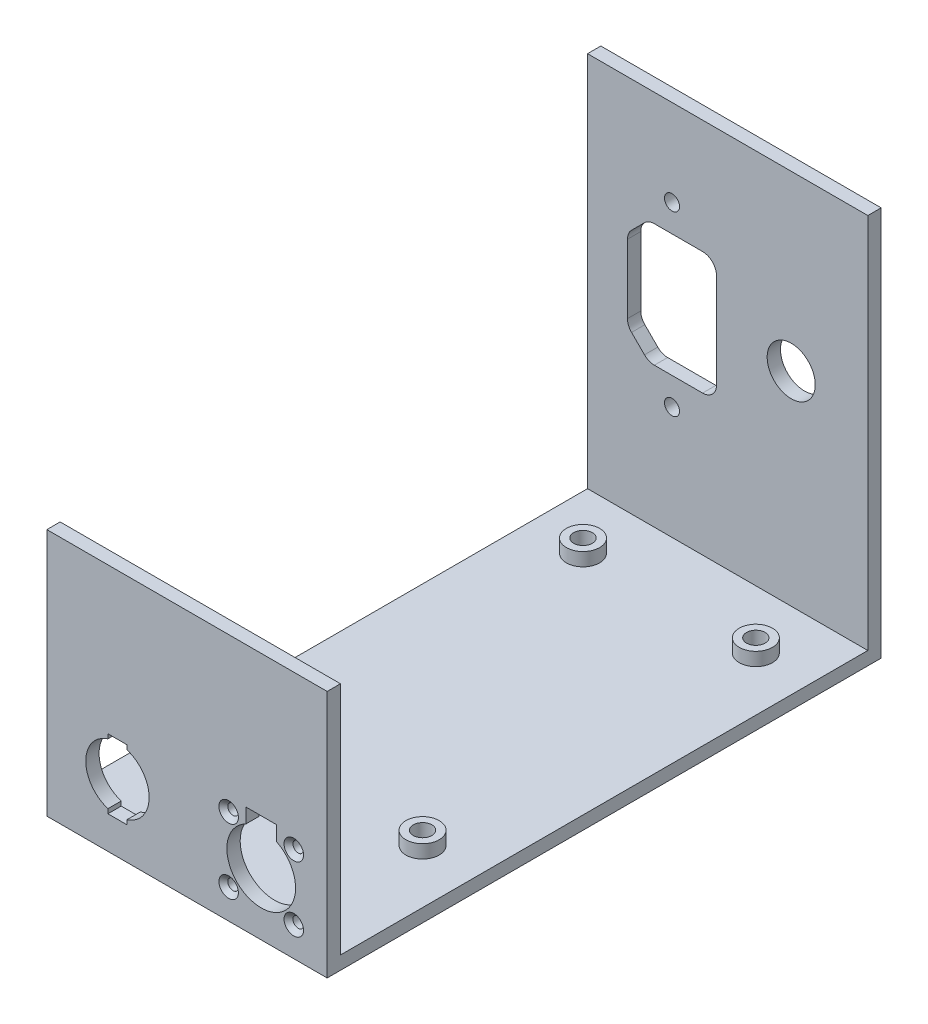
SolidWorks part; units mm, degrees
ref_plane "Спереди" through (0, 0, 0) normal (0, 0, 1) x (1, 0, 0)
ref_plane "Сверху" through (0, 0, 0) normal (0, 1, 0) x (1, 0, 0)
ref_plane "Справа" through (0, 0, 0) normal (1, 0, 0) x (0, 0, -1)
sketch "Эскиз2" plane through (0, 0, 0) normal (0, -1, 0) x (1, 0, 0)
  circle A0 centre (19.5, 37.6) radius 3.75
  circle A1 centre (19.5, -37.6) radius 3.75
  circle A2 centre (-19.5, -37.6) radius 3.75
  circle A3 centre (-19.5, 37.6) radius 3.75
  dimension "D1" = 7.5
extrude "Бобышка-Вытянуть1" add sketch "Эскиз2" along normal blind 3
sketch "Эскиз3" plane through (0, -3, 0) normal (0, -1, 0) x (1, 0, 0)
  line L0 (26.625, 41.25) -> (26.625, -41.25) construction
  line L1 (-31.625, 71.25) -> (31.625, 71.25)
  line L2 (-31.625, 71.25) -> (-31.625, -53.75)
  line L3 (-31.625, -53.75) -> (31.625, -53.75)
  line L4 (31.625, 71.25) -> (31.625, -53.75)
  line L5 (-31.625, 71.25) -> (31.625, -53.75) construction
  line L6 (-31.625, -53.75) -> (31.625, 71.25) construction
  line L8 (-23.625, 41.25) -> (23.625, 41.25) construction
  line L9 (-26.625, 41.25) -> (-26.625, -41.25) construction
  point P0 (0, 8.75)
  dimension "D1" = 5
  dimension "D2" = 125
  dimension "D3" = 30
  dimension "D4" = 5
extrude "Бобышка-Вытянуть2" add sketch "Эскиз3" along normal blind 3
sketch "Эскиз4" plane through (0, 0, 0) normal (0, 1, 0) x (1, 0, 0)
  circle A0 centre (19.5, 37.6) radius 2.1
  circle A1 centre (19.5, -37.6) radius 2.1
  circle A2 centre (-19.5, -37.6) radius 2.1
  circle A3 centre (-19.5, 37.6) radius 2.1
  dimension "D1" = 4.2
extrude "Вырез-Вытянуть1" cut sketch "Эскиз4" against normal blind 4
sketch "Эскиз5" plane through (0, -3, 0) normal (0, 1, 0) x (1, 0, 0)
  line L0 (31.625, 53.75) -> (31.625, -71.25) construction
  line L1 (-31.625, -71.25) -> (31.625, -71.25)
  line L2 (-31.625, -71.25) -> (-31.625, -68.25)
  line L3 (-31.625, -68.25) -> (31.625, -68.25)
  line L4 (31.625, -71.25) -> (31.625, -68.25)
  dimension "D1" = 3
extrude "Бобышка-Вытянуть3" add sketch "Эскиз5" along normal blind 53
sketch "Эскиз8" plane through (0, 0, 71.25) normal (0, 0, 1) x (1, 0, 0)
  line L6 (20.1954, 14.9397) -> (20.1954, 18.25)
  line L7 (20.1954, 18.25) -> (13.2954, 18.25)
  line L8 (13.2954, 18.25) -> (13.2954, 14.9397)
  line L9 (20.1954, 14.9397) -> (20.1954, 18.25)
  line L10 (20.1954, 18.25) -> (13.2954, 18.25)
  line L11 (13.2954, 18.25) -> (13.2954, 14.9397)
  arc A2 (13.2954, 14.9397) -> (20.1954, 14.9397) centre (16.7454, 8) ccw
  arc A3 (13.2954, 14.9397) -> (20.1954, 14.9397) centre (16.7454, 8) ccw
  dimension "D1" = 0.15
extrude "Вырез-Вытянуть2" cut sketch "Эскиз8" against normal blind 10
hole_wizard "Зенковка для винта с полупотайной головкой M21" positions "Эскиз9" profile "Эскиз11" countersink size "M2" standard "DIN"
sketch "Эскиз9" plane through (0, 0, 71.25) normal (0, 0, 1) x (1, 0, 0)
  circle A0 centre (9.3954, 0.65) radius 1.2 construction
  circle A1 centre (24.0954, 0.65) radius 1.2 construction
  circle A2 centre (9.3954, 15.35) radius 1.2 construction
  circle A3 centre (24.0954, 15.35) radius 1.2 construction
  circle A4 centre (9.3954, 0.65) radius 1.2 construction
  circle A5 centre (24.0954, 0.65) radius 1.2 construction
  circle A6 centre (9.3954, 15.35) radius 1.2 construction
  circle A7 centre (24.0954, 15.35) radius 1.2 construction
  point P1 (9.3954, 0.65)
  point P3 (24.0954, 0.65)
  point P5 (9.3954, 15.35)
  point P7 (24.0954, 15.35)
sketch "Эскиз11" plane through (9.3954, 0.65, 71.25) normal (1, 0, 0) x (0, -1, 0)
  line L0 (0, 0) -> (0, 5.721)
  line L1 (0, 5.721) -> (1.2, 5)
  line L2 (1.2, 5) -> (1.2, 1)
  line L3 (1.2, 1) -> (2.2, 0)
  line L5 (2.2, 0) -> (0, 0)
  line L6 (-1.2, 1) -> (-2.2, 0) construction
  line L10 (0, 5.721) -> (-1.2, 5) construction
  line L11 (0, -6.35) -> (0, 107.95) construction
  dimension "Диаметр отверстия" = 2.4
  dimension "Глубина отверстия" = 5
  dimension "Диаметр передней зенковки" = 4.4
  dimension "Угол передней зенковки" = 90
  dimension "Угол заточки сверла" = 118
sketch "Эскиз12" plane through (0, -3, 0) normal (0, 1, 0) x (1, 0, 0)
  line L0 (-31.625, -68.25) -> (-31.625, 53.75) construction
  line L1 (31.625, 53.75) -> (-31.625, 53.75)
  line L2 (31.625, 53.75) -> (31.625, 50.75)
  line L3 (31.625, 50.75) -> (-31.625, 50.75)
  line L4 (-31.625, 53.75) -> (-31.625, 50.75)
  dimension "D1" = 3
extrude "Бобышка-Вытянуть4" add sketch "Эскиз12" along normal blind 85
sketch "Эскиз13" plane through (0, 0, -50.75) normal (0, 0, 1) x (1, 0, 0)
  line L12 (-16.5476, 28.6612) -> (-5.6652, 28.6612)
  line L13 (-2.5152, 31.8112) -> (-2.5152, 53.1612)
  line L14 (-5.6652, 56.3112) -> (-16.5476, 56.3112)
  line L15 (-18.775, 55.3886) -> (-21.6926, 52.471)
  line L16 (-22.6152, 50.2436) -> (-22.6152, 34.7289)
  line L17 (-21.6926, 32.5015) -> (-18.775, 29.5839)
  line L18 (-16.5476, 28.6612) -> (-5.6652, 28.6612)
  line L19 (-2.5152, 31.8112) -> (-2.5152, 53.1612)
  line L20 (-5.6652, 56.3112) -> (-16.5476, 56.3112)
  line L21 (-18.775, 55.3886) -> (-21.6926, 52.471)
  line L22 (-22.6152, 50.2436) -> (-22.6152, 34.7289)
  line L23 (-21.6926, 32.5015) -> (-18.775, 29.5839)
  arc A12 (-18.775, 29.5839) -> (-16.5476, 28.6612) centre (-16.5476, 31.8112) ccw
  arc A13 (-5.6652, 28.6612) -> (-2.5152, 31.8112) centre (-5.6652, 31.8112) ccw
  arc A14 (-2.5152, 53.1612) -> (-5.6652, 56.3112) centre (-5.6652, 53.1612) ccw
  arc A15 (-16.5476, 56.3112) -> (-18.775, 55.3886) centre (-16.5476, 53.1612) ccw
  arc A16 (-21.6926, 52.471) -> (-22.6152, 50.2436) centre (-19.4652, 50.2436) ccw
  arc A17 (-22.6152, 34.7289) -> (-21.6926, 32.5015) centre (-19.4652, 34.7289) ccw
  arc A18 (-18.775, 29.5839) -> (-16.5476, 28.6612) centre (-16.5476, 31.8112) ccw
  arc A19 (-5.6652, 28.6612) -> (-2.5152, 31.8112) centre (-5.6652, 31.8112) ccw
  arc A20 (-2.5152, 53.1612) -> (-5.6652, 56.3112) centre (-5.6652, 53.1612) ccw
  arc A21 (-16.5476, 56.3112) -> (-18.775, 55.3886) centre (-16.5476, 53.1612) ccw
  arc A22 (-21.6926, 52.471) -> (-22.6152, 50.2436) centre (-19.4652, 50.2436) ccw
  arc A23 (-22.6152, 34.7289) -> (-21.6926, 32.5015) centre (-19.4652, 34.7289) ccw
  dimension "D1" = 0.15
extrude "Вырез-Вытянуть3" cut sketch "Эскиз13" against normal through all
hole_wizard "Отверстие с зазором M31" positions "Эскиз14" profile "Эскиз15" hole size "M3" standard "DIN"
sketch "Эскиз14" plane through (0, 0, -53.75) normal (0, 0, -1) x (-1, 0, 0)
  point P0 (12.5652, 22.4862)
  point P3 (12.5652, 62.4862)
sketch "Эскиз15" plane through (-12.5652, 22.4862, -53.75) normal (1, 0, 0) x (0, 1, 0)
  line L0 (0, 0) -> (0, 11.0215)
  line L1 (0, 11.0215) -> (1.7, 10)
  line L2 (1.7, 10) -> (1.7, 0)
  line L5 (1.7, 0) -> (0, 0)
  line L10 (0, 11.0215) -> (-1.7, 10) construction
  line L11 (0, -6.35) -> (0, 107.95) construction
  dimension "Диаметр отверстия" = 3.4
  dimension "Глубина отверстия" = 10
  dimension "Угол заточки сверла" = 118
sketch "Эскиз16" plane through (0, 0, -50.75) normal (0, 0, 1) x (1, 0, 0)
  circle A2 centre (14.3322, 42.9731) radius 5.425
  circle A3 centre (14.3322, 42.9731) radius 5.425
  dimension "D1" = 0.15
extrude "Вырез-Вытянуть4" cut sketch "Эскиз16" against normal through all
sketch "Эскиз17" plane through (0, 0, 68.25) normal (0, 0, -1) x (-1, 0, 0)
  line L2 (17.6969, 0.8798) -> (13.6969, 0.8798) construction
  line L3 (17.6969, 17.4672) -> (13.6969, 17.4672) construction
  line L8 (17.6969, 1.0406) -> (17.6969, 0.8798) construction
  line L9 (13.6969, 1.0406) -> (13.6969, 0.8798) construction
  line L10 (13.6969, 17.3064) -> (13.6969, 17.4672) construction
  line L11 (17.6969, 17.3064) -> (17.6969, 17.4672) construction
  line L12 (17.6969, 0.8798) -> (13.6969, 0.8798) construction
  line L13 (17.6969, 17.4672) -> (13.6969, 17.4672) construction
  line L14 (17.6969, 2.4653) -> (17.6969, 0.8798) construction
  line L15 (13.6969, 2.4653) -> (13.6969, 0.8798) construction
  line L16 (13.6969, 15.8817) -> (13.6969, 17.4672) construction
  line L17 (17.6969, 15.8817) -> (17.6969, 17.4672) construction
  line L18 (13.5469, 15.9926) -> (13.5469, 16.9926)
  line L19 (13.5469, 2.3544) -> (13.5469, 1.3544)
  line L22 (17.8469, 2.3544) -> (17.8469, 1.3544)
  line L23 (17.8469, 15.9926) -> (17.8469, 16.9926)
  line L24 (17.8469, 15.9926) -> (17.8469, 17.4672) construction
  line L25 (13.5469, 15.9926) -> (13.5469, 17.4672) construction
  line L26 (17.8469, 16.9926) -> (13.5469, 16.9926)
  line L27 (13.5469, 2.3544) -> (13.5469, 0.8798) construction
  line L28 (17.8469, 2.3544) -> (17.8469, 0.8798) construction
  line L29 (17.8469, 1.3544) -> (13.5469, 1.3544)
  arc A0 (18.8493, 2.9235) -> (18.8493, 15.4235) centre (15.6969, 9.1735) ccw construction
  arc A1 (13.6969, 15.8817) -> (13.6969, 2.4653) centre (15.6969, 9.1735) ccw construction
  arc A2 (17.6969, 2.4653) -> (17.6969, 15.8817) centre (15.6969, 9.1735) ccw construction
  arc A5 (13.5469, 15.9926) -> (13.5469, 2.3544) centre (15.6969, 9.1735) ccw
  arc A6 (17.8469, 2.3544) -> (17.8469, 15.9926) centre (15.6969, 9.1735) ccw
  dimension "D2" = 1
  dimension "D3" = 1
  dimension "D1" = 0.15
extrude "Вырез-Вытянуть5" cut sketch "Эскиз17" against normal through all
